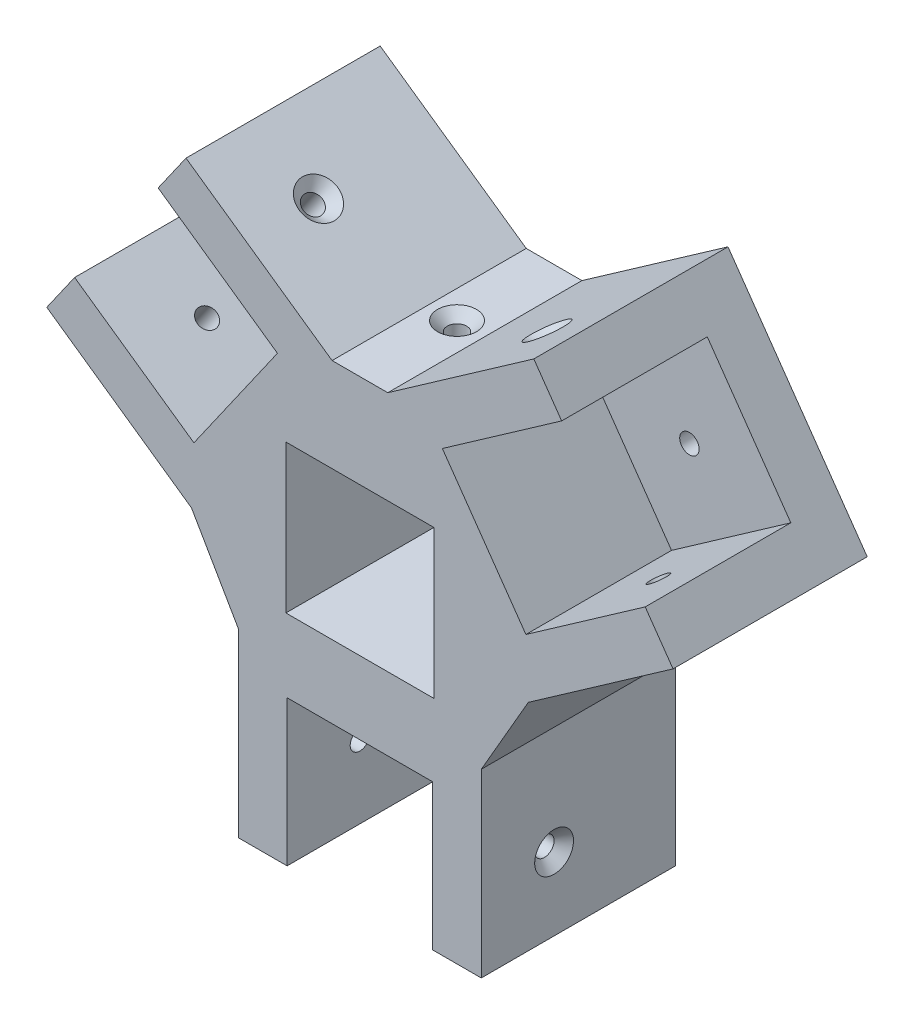
SolidWorks part; units mm, degrees
ref_plane "Top Plane" through (0, 0, 0) normal (0, 0, 1) x (1, 0, 0)
ref_plane "Right Plane" through (0, 0, 0) normal (0, 1, 0) x (1, 0, 0)
ref_plane "Front Plane" through (0, 0, 0) normal (1, 0, 0) x (0, 0, -1)
sketch "Sketch1" plane through (0, 0, 0) normal (0, 0, 1) x (1, 0, 0)
  line L0 (-25, -60.25) -> (-25, -13.0142)
  line L1 (-25, -13.0142) -> (-64.5036, 14.6465)
  line L2 (-64.5036, 14.6465) -> (-35.8247, 55.6041)
  line L3 (-35.8247, 55.6041) -> (0, 30.5194)
  line L4 (0, 30.5194) -> (35.8247, 55.6041)
  line L5 (35.8247, 55.6041) -> (64.5036, 14.6465)
  line L6 (64.5036, 14.6465) -> (25, -13.0142)
  line L7 (25, -13.0142) -> (25, -60.25)
  line L8 (25, -60.25) -> (-25, -60.25)
  line L9 (0, 30.5194) -> (0, 0) construction
  line L10 (0, 0) -> (0, -60.25) construction
  line L11 (-35.8247, 55.6041) -> (35.8247, 55.6041) construction
  line L12 (0, 55.6041) -> (0, 30.5194) construction
  line L13 (0, 0) -> (50.1641, 35.1253) construction
  line L14 (-15.25, -15.25) -> (15.25, -15.25)
  line L15 (-15.25, -15.25) -> (-15.25, 15.25)
  line L16 (-15.25, 15.25) -> (15.25, 15.25)
  line L17 (15.25, -15.25) -> (15.25, 15.25)
  line L18 (-15.25, -15.25) -> (15.25, 15.25) construction
  line L19 (-15.25, 15.25) -> (15.25, -15.25) construction
  line L20 (3.0586, 32.6611) -> (31.7375, -8.2965) construction
  dimension "D1" = 30.5
  dimension "D2" = 45
  dimension "D3" = 50
  dimension "D4" = 40
  dimension "D5" = 110
extrude "Boss-Extrude1" add sketch "Sketch1" along normal blind 10
sketch "Sketch2" plane through (0, 0, 10) normal (0, 0, 1) x (1, 0, 0)
  line L1 (-58.7678, 22.838) -> (-34.1932, 5.6307)
  line L2 (-41.5605, 47.4126) -> (-16.9859, 30.2053)
  line L3 (-34.1932, 5.6307) -> (-16.9859, 30.2053)
  line L5 (41.5605, 47.4126) -> (16.9859, 30.2053)
  line L6 (58.7678, 22.838) -> (34.1932, 5.6307)
  line L7 (16.9859, 30.2053) -> (34.1932, 5.6307)
  line L9 (-25, -60.25) -> (25, -60.25)
  line L10 (25, -60.25) -> (25, -13.0142)
  line L11 (25, -13.0142) -> (64.5036, 14.6465)
  line L12 (64.5036, 14.6465) -> (35.8247, 55.6041)
  line L13 (35.8247, 55.6041) -> (0, 30.5194)
  line L14 (0, 30.5194) -> (-35.8247, 55.6041)
  line L15 (-35.8247, 55.6041) -> (-64.5036, 14.6465)
  line L16 (-64.5036, 14.6465) -> (-25, -13.0142)
  line L17 (-25, -13.0142) -> (-25, -60.25)
  line L18 (-25, -60.25) -> (-15, -60.25)
  line L19 (25, -60.25) -> (25, -13.0142)
  line L20 (25, -13.0142) -> (64.5036, 14.6465)
  line L21 (64.5036, 14.6465) -> (58.7678, 22.838)
  line L22 (35.8247, 55.6041) -> (0, 30.5194)
  line L23 (0, 30.5194) -> (-35.8247, 55.6041)
  line L24 (-35.8247, 55.6041) -> (-41.5605, 47.4126)
  line L25 (-64.5036, 14.6465) -> (-25, -13.0142)
  line L26 (-25, -13.0142) -> (-25, -60.25)
  line L27 (-15, -60.25) -> (-15, -30.25)
  line L28 (15, -60.25) -> (15, -30.25)
  line L29 (-15, -30.25) -> (15, -30.25)
  line L30 (-58.7678, 22.838) -> (-64.5036, 14.6465)
  line L31 (41.5605, 47.4126) -> (35.8247, 55.6041)
  line L32 (15, -60.25) -> (25, -60.25)
  line L33 (-15.25, 15.25) -> (15.25, 15.25)
  line L34 (-15.25, 15.25) -> (-15.25, -15.25)
  line L35 (15.25, 15.25) -> (15.25, -15.25)
  line L36 (-15.25, -15.25) -> (15.25, -15.25)
  line L37 (-25, -60.25) -> (25, -60.25) construction
  line L38 (64.5036, 14.6465) -> (35.8247, 55.6041) construction
  point P2 (15.25, -11.9993)
  point P24 (15.25, -25.25)
  dimension "D2" = 10
  dimension "D3" = 30
  dimension "D1" = 0
extrude "Boss-Extrude2" add sketch "Sketch2" along normal blind 30
chamfer "Chamfer1" distance 10 angle 30 2 edges at (-25, -13.0142, 20) (25, -13.0142, 20) first distance on face at (-25, -36.6321, 20) first distance on face at (25, -36.6321, 20)
fillet "Chamfer2" radius 10 1 edges at (0, 30.5194, 20) profile chamfer
sketch "Sketch3" plane through (0, 0, 10) normal (0, 0, 1) x (1, 0, 0)
  line L0 (34.1932, 5.6307) -> (41.5605, 47.4126) construction
  line L2 (15, -60.25) -> (-15, -30.25) construction
  line L4 (-34.1932, 5.6307) -> (-41.5605, 47.4126) construction
  circle A0 centre (37.8769, 26.5217) radius 2
  circle A1 centre (0, -45.25) radius 2
  circle A2 centre (-37.8769, 26.5217) radius 2
  dimension "D1" = 4
extrude "Cut-Extrude1" cut sketch "Sketch3" against normal through all
sketch "Sketch4" plane through (-14.3394, 20.4788, 0) normal (-0.5736, 0.8192, 0) x (0.8192, 0.5736, 0)
  line L0 (61.2391, -10) -> (31.2391, -40) construction
  circle A0 centre (46.2391, -25) radius 2
  dimension "D1" = 4
extrude "Cut-Extrude2" cut sketch "Sketch4" against normal through all
sketch "Sketch5" plane through (25, 0, 0) normal (1, 0, 0) x (0, 0, -1)
  line L0 (-40, -60.25) -> (-10, -30.25) construction
  circle A0 centre (-25, -45.25) radius 2
  dimension "D1" = 4
extrude "Cut-Extrude3" cut sketch "Sketch5" against normal blind 30
mirror "Mirror1" about plane through (0, 0, 0) normal (1, 0, 0) of "Cut-Extrude2", "Cut-Extrude3"
sketch "Sketch6" plane through (0, 34.5356, 0) normal (0, 1, 0) x (1, 0, 0)
  line L0 (0, 0) -> (0, -40) construction
  line L1 (-5.7358, 0) -> (5.7358, 0) construction
  line L2 (5.7358, -40) -> (-5.7358, -40) construction
  circle A0 centre (0, -20) radius 2
  dimension "D1" = 4
extrude "Cut-Extrude4" cut sketch "Sketch6" against normal through all
chamfer "Chamfer3" distance 2 angle 45 11 edges at (2, -45.25, 0) (21.8991, 45.8533, 25) (25, -43.25, 25) (39.8769, 26.5217, 0) (50.578, 4.8957, 25) (-25, -43.25, 25) (-53.8546, 7.19, 25) (-21.8991, 45.8533, 25) (-35.8769, 26.5217, 0) (-2, -30.25, 20) (0, 34.5356, 22)
